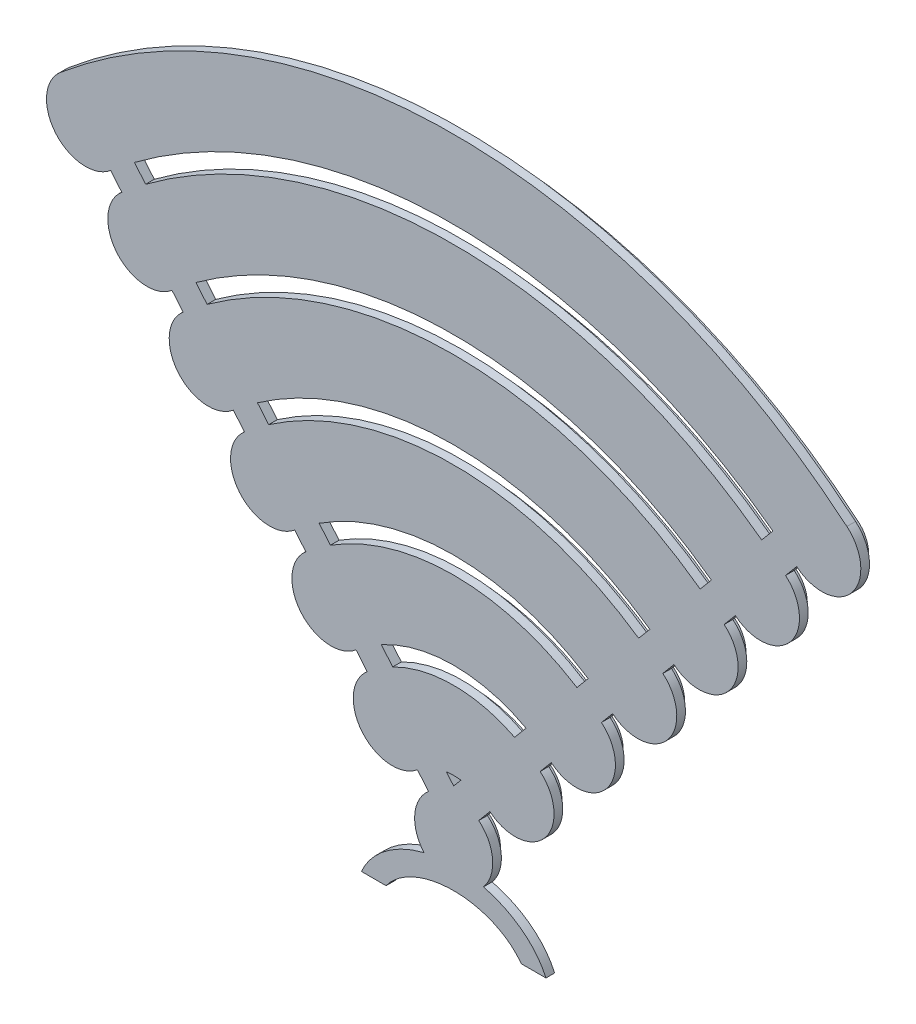
SolidWorks part; units mm, degrees
ref_plane "Front Plane" through (0, 0, 0) normal (0, 0, 1) x (1, 0, 0)
ref_plane "Top Plane" through (0, 0, 0) normal (0, 1, 0) x (1, 0, 0)
ref_plane "Right Plane" through (0, 0, 0) normal (1, 0, 0) x (0, 0, -1)
sketch "Sketch1" plane through (0, 0, 0) normal (0, 0, 1) x (1, 0, 0)
  line L0 (-84.848, 101.1179) -> (-70.7066, 84.2649) construction
  line L1 (-70.7066, 84.2649) -> (-56.5653, 67.4119) construction
  line L2 (-56.5653, 67.4119) -> (-42.424, 50.5589) construction
  line L3 (-42.424, 50.5589) -> (-28.2827, 33.706) construction
  line L4 (-28.2827, 33.706) -> (-14.1413, 16.853) construction
  line L5 (-14.1413, 16.853) -> (0, 0) construction
  line L6 (0, 172.6886) -> (0, -139.3712) construction
  line L7 (-79.0629, 94.2235) -> (-76.4917, 91.1593)
  line L8 (-64.9215, 77.3705) -> (-62.3504, 74.3063)
  line L9 (-50.7802, 60.5175) -> (-48.2091, 57.4533)
  line L10 (-36.6389, 43.6645) -> (-34.0677, 40.6004)
  line L11 (-22.4976, 26.8116) -> (-19.9264, 23.7474)
  line L12 (-8.3562, 9.9586) -> (-5.7851, 6.8944)
  line L13 (-73.5724, 98.5703) -> (-70.997, 95.501)
  line L14 (-59.4031, 81.684) -> (-56.8255, 78.6121)
  line L15 (-45.2182, 64.779) -> (-42.6363, 61.7021)
  line L16 (-30.9992, 47.8335) -> (-28.407, 44.7442)
  line L17 (-16.6807, 30.7694) -> (-14.0494, 27.6335)
  line L18 (-1.6791, 12.8911) -> (0, 10.8901)
  line L19 (14.1413, 16.853) -> (0, 0) construction
  line L20 (28.2827, 33.706) -> (14.1413, 16.853) construction
  line L21 (42.424, 50.5589) -> (28.2827, 33.706) construction
  line L22 (56.5653, 67.4119) -> (42.424, 50.5589) construction
  line L23 (70.7066, 84.2649) -> (56.5653, 67.4119) construction
  line L24 (84.848, 101.1179) -> (70.7066, 84.2649) construction
  line L25 (1.6791, 12.8911) -> (0, 10.8901)
  line L26 (16.6807, 30.7694) -> (14.0494, 27.6335)
  line L27 (30.9992, 47.8335) -> (28.407, 44.7442)
  line L28 (45.2182, 64.779) -> (42.6363, 61.7021)
  line L29 (59.4031, 81.684) -> (56.8255, 78.6121)
  line L30 (73.5724, 98.5703) -> (70.997, 95.501)
  line L31 (8.3562, 9.9586) -> (5.7851, 6.8944)
  line L32 (22.4976, 26.8116) -> (19.9264, 23.7474)
  line L33 (36.6389, 43.6645) -> (34.0677, 40.6004)
  line L34 (50.7802, 60.5175) -> (48.2091, 57.4533)
  line L35 (64.9215, 77.3705) -> (62.3504, 74.3063)
  line L36 (79.0629, 94.2235) -> (76.4917, 91.1593)
  line L37 (15.5746, -16.8) -> (21.273, -16.8)
  line L38 (0, -10) -> (0, -5) construction
  line L39 (-17.5, -22.5) -> (-22.5, -22.5) construction
  line L40 (-21.273, -16.8) -> (-15.5746, -16.8)
  line L41 (-15.5935, -17) -> (15.5935, -17) construction
  arc A0 (-5.7851, 6.8944) -> (-6.8548, -5.8319) centre (0, 0) ccw
  arc A1 (14.0494, 27.6335) -> (-14.0494, 27.6335) centre (0, 0) ccw
  arc A2 (1.6791, 12.8911) -> (-1.6791, 12.8911) centre (0, 0) ccw
  arc A3 (28.407, 44.7442) -> (-28.407, 44.7442) centre (0, 0) ccw
  arc A4 (16.6807, 30.7694) -> (-16.6807, 30.7694) centre (0, 0) ccw
  arc A5 (30.9992, 47.8335) -> (-30.9992, 47.8335) centre (0, 0) ccw
  arc A6 (42.6363, 61.7021) -> (-42.6363, 61.7021) centre (0, 0) ccw
  arc A7 (45.2182, 64.779) -> (-45.2182, 64.779) centre (0, 0) ccw
  arc A8 (56.8255, 78.6121) -> (-56.8255, 78.6121) centre (0, 0) ccw
  arc A9 (59.4031, 81.684) -> (-59.4031, 81.684) centre (0, 0) ccw
  arc A10 (70.997, 95.501) -> (-70.997, 95.501) centre (0, 0) ccw
  arc A11 (-19.9264, 23.7474) -> (-8.3562, 9.9586) centre (-14.1413, 16.853) ccw
  arc A12 (-34.0677, 40.6004) -> (-22.4976, 26.8116) centre (-28.2827, 33.706) ccw
  arc A13 (-48.2091, 57.4533) -> (-36.6389, 43.6645) centre (-42.424, 50.5589) ccw
  arc A14 (-62.3504, 74.3063) -> (-50.7802, 60.5175) centre (-56.5653, 67.4119) ccw
  arc A15 (-76.4917, 91.1593) -> (-64.9215, 77.3705) centre (-70.7066, 84.2649) ccw
  arc A16 (73.5724, 98.5703) -> (-73.5724, 98.5703) centre (0, 0) ccw
  arc A17 (90.6331, 108.0123) -> (-90.6331, 108.0123) centre (0, 0) ccw
  arc A18 (-90.6331, 108.0123) -> (-79.0629, 94.2235) centre (-84.848, 101.1179) ccw
  arc A19 (-5.7851, 6.8944) -> (5.7851, 6.8944) centre (0, 0) ccw construction
  arc A20 (90.6331, 108.0123) -> (79.0629, 94.2235) centre (84.848, 101.1179) cw
  arc A21 (76.4917, 91.1593) -> (64.9215, 77.3705) centre (70.7066, 84.2649) cw
  arc A22 (62.3504, 74.3063) -> (50.7802, 60.5175) centre (56.5653, 67.4119) cw
  arc A23 (48.2091, 57.4533) -> (36.6389, 43.6645) centre (42.424, 50.5589) cw
  arc A24 (34.0677, 40.6004) -> (22.4976, 26.8116) centre (28.2827, 33.706) cw
  arc A25 (19.9264, 23.7474) -> (8.3562, 9.9586) centre (14.1413, 16.853) cw
  arc A26 (6.8548, -5.8319) -> (5.7851, 6.8944) centre (0, 0) ccw
  ellipse E0 centre (0, -22.5) end of major axis (22.5, -22.5) minor radius 17.5 (21.273, -16.8) -> (6.8548, -5.8319) ccw
  ellipse E1 centre (0, -22.5) end of major axis (-17.5, -22.5) minor radius 12.5 (15.5746, -16.8) -> (-15.5746, -16.8) ccw
  ellipse E2 centre (0, -22.5) end of major axis (22.5, -22.5) minor radius 17.5 (-21.273, -16.8) -> (-6.8548, -5.8319) cw
  point P42 (0, -9)
  point P67 (0, 141)
  point P86 (-20, -22.5)
  point P91 (0, 0)
  point P94 (0, 0)
  dimension "D2" = 9
  dimension "D1" = 40
  dimension "D3" = 150
  dimension "D4" = 7
  dimension "D5" = 5
  dimension "D6" = 20
  dimension "D7" = 12.5
  dimension "D8" = 5
  dimension "D9" = 0.2
  dimension "D10" = 5
extrude "Boss-Extrude1" add sketch "Sketch1" along normal blind 1 and the other way blind 1
sketch "Sketch2" plane through (0, 0, -1) normal (0, 0, -1) x (-1, 0, 0)
  line L24 (30.7332, 40.049) -> (36.6028, 47.0441)
  line L25 (44.8746, 56.902) -> (50.7441, 63.8971)
  line L26 (59.0159, 73.755) -> (64.8855, 80.7501)
  line L27 (73.1572, 90.608) -> (79.0268, 97.6031)
  line L28 (-79.0268, 97.6031) -> (-73.1572, 90.608)
  line L29 (-64.8855, 80.7501) -> (-59.0159, 73.755)
  line L30 (-50.7441, 63.8971) -> (-44.8746, 56.902)
  line L31 (-36.6028, 47.0441) -> (-30.7332, 40.049)
  line L32 (-22.4615, 30.1911) -> (-16.5919, 23.1961)
  line L33 (-8.3202, 13.3382) -> (-2.4506, 6.3431)
  line L34 (2.4506, 6.3431) -> (8.3202, 13.3382)
  line L35 (16.5919, 23.1961) -> (22.4615, 30.1911)
  circle A1 centre (0, 0) radius 6.8
  arc A2 (74.8884, 100.3333) -> (-74.8884, 100.3333) centre (0, 0) ccw
  arc A3 (80.477, 95.9088) -> (-80.477, 95.9088) centre (0, 0) ccw
  arc A4 (6.8548, -5.8319) -> (5.7851, 6.8944) centre (0, 0) ccw construction
  arc A5 (81.7626, 97.4409) -> (-81.7626, 97.4409) centre (0, 0) ccw
  arc A6 (-87.9333, 104.7949) -> (-81.7626, 97.4409) centre (-84.848, 101.1179) ccw
  arc A7 (87.9333, 104.7949) -> (-87.9333, 104.7949) centre (0, 0) ccw
  arc A8 (81.7626, 97.4409) -> (87.9333, 104.7949) centre (84.848, 101.1179) ccw
  arc A9 (73.792, 87.9419) -> (-73.792, 87.9419) centre (0, 0) ccw
  arc A10 (-73.792, 87.9419) -> (-67.6213, 80.5879) centre (-70.7066, 84.2649) ccw
  arc A11 (67.6213, 80.5879) -> (-67.6213, 80.5879) centre (0, 0) ccw
  arc A12 (69.6844, 93.7354) -> (-69.6844, 93.7354) centre (0, 0) ccw
  arc A13 (75.0776, 89.474) -> (-75.0776, 89.474) centre (0, 0) ccw
  arc A14 (67.6213, 80.5879) -> (73.792, 87.9419) centre (70.7066, 84.2649) ccw
  arc A15 (25.1973, 30.0289) -> (31.368, 37.383) centre (28.2827, 33.706) ccw
  arc A16 (31.368, 37.383) -> (-31.368, 37.383) centre (0, 0) ccw
  arc A17 (-31.368, 37.383) -> (-25.1973, 30.0289) centre (-28.2827, 33.706) ccw
  arc A18 (25.1973, 30.0289) -> (-25.1973, 30.0289) centre (0, 0) ccw
  arc A19 (39.3386, 46.8819) -> (45.5094, 54.2359) centre (42.424, 50.5589) ccw
  arc A20 (45.5094, 54.2359) -> (-45.5094, 54.2359) centre (0, 0) ccw
  arc A21 (-45.5094, 54.2359) -> (-39.3386, 46.8819) centre (-42.424, 50.5589) ccw
  arc A22 (39.3386, 46.8819) -> (-39.3386, 46.8819) centre (0, 0) ccw
  arc A23 (53.4799, 63.7349) -> (59.6507, 71.0889) centre (56.5653, 67.4119) ccw
  arc A24 (59.6507, 71.0889) -> (-59.6507, 71.0889) centre (0, 0) ccw
  arc A25 (-59.6507, 71.0889) -> (-53.4799, 63.7349) centre (-56.5653, 67.4119) ccw
  arc A26 (53.4799, 63.7349) -> (-53.4799, 63.7349) centre (0, 0) ccw
  arc A27 (-17.2267, 20.53) -> (-11.0559, 13.176) centre (-14.1413, 16.853) ccw
  arc A28 (22.4615, 30.1911) -> (30.7332, 40.049) centre (28.2827, 33.706) ccw
  arc A29 (36.6028, 47.0441) -> (44.8746, 56.902) centre (42.424, 50.5589) ccw
  arc A30 (50.7441, 63.8971) -> (59.0159, 73.755) centre (56.5653, 67.4119) ccw
  arc A31 (64.8855, 80.7501) -> (73.1572, 90.608) centre (70.7066, 84.2649) ccw
  arc A32 (79.0268, 97.6031) -> (89.2189, 106.327) centre (84.848, 101.1179) ccw
  arc A33 (89.2189, 106.327) -> (-89.2189, 106.327) centre (0, 0) ccw
  arc A34 (-89.2189, 106.327) -> (-79.0268, 97.6031) centre (-84.848, 101.1179) ccw
  arc A35 (-73.1572, 90.608) -> (-64.8855, 80.7501) centre (-70.7066, 84.2649) ccw
  arc A36 (-59.0159, 73.755) -> (-50.7441, 63.8971) centre (-56.5653, 67.4119) ccw
  arc A37 (-44.8746, 56.902) -> (-36.6028, 47.0441) centre (-42.424, 50.5589) ccw
  arc A38 (-30.7332, 40.049) -> (-22.4615, 30.1911) centre (-28.2827, 33.706) ccw
  arc A39 (-16.5919, 23.1961) -> (-8.3202, 13.3382) centre (-14.1413, 16.853) ccw
  arc A40 (-2.4506, 6.3431) -> (2.4506, 6.3431) centre (0, 0) ccw
  arc A41 (8.3202, 13.3382) -> (16.5919, 23.1961) centre (14.1413, 16.853) ccw
  arc A42 (23.9117, 28.4969) -> (32.6536, 38.9151) centre (28.2827, 33.706) ccw
  arc A43 (38.053, 45.3498) -> (46.7949, 55.768) centre (42.424, 50.5589) ccw
  arc A44 (52.1944, 62.2028) -> (60.9363, 72.621) centre (56.5653, 67.4119) ccw
  arc A45 (66.3357, 79.0558) -> (75.0776, 89.474) centre (70.7066, 84.2649) ccw
  arc A46 (80.477, 95.9088) -> (89.2189, 106.327) centre (84.848, 101.1179) ccw
  arc A47 (89.2189, 106.327) -> (-89.2189, 106.327) centre (0, 0) ccw
  arc A48 (-89.2189, 106.327) -> (-80.477, 95.9088) centre (-84.848, 101.1179) ccw
  arc A49 (-75.0776, 89.474) -> (-66.3357, 79.0558) centre (-70.7066, 84.2649) ccw
  arc A50 (-60.9363, 72.621) -> (-52.1944, 62.2028) centre (-56.5653, 67.4119) ccw
  arc A51 (-46.7949, 55.768) -> (-38.053, 45.3498) centre (-42.424, 50.5589) ccw
  arc A52 (-32.6536, 38.9151) -> (-23.9117, 28.4969) centre (-28.2827, 33.706) ccw
  arc A53 (-18.5123, 22.0621) -> (-9.7704, 11.6439) centre (-14.1413, 16.853) ccw
  arc A54 (11.0559, 13.176) -> (-11.0559, 13.176) centre (0, 0) ccw
  arc A55 (9.7704, 11.6439) -> (18.5123, 22.0621) centre (14.1413, 16.853) ccw
  arc A56 (11.0559, 13.176) -> (17.2267, 20.53) centre (14.1413, 16.853) ccw
  arc A57 (60.6971, 83.4632) -> (-60.6971, 83.4632) centre (0, 0) ccw
  arc A58 (66.3357, 79.0558) -> (-66.3357, 79.0558) centre (0, 0) ccw
  arc A59 (17.2267, 20.53) -> (-17.2267, 20.53) centre (0, 0) ccw
  arc A60 (55.5367, 76.8291) -> (-55.5367, 76.8291) centre (0, 0) ccw
  arc A61 (60.9363, 72.621) -> (-60.9363, 72.621) centre (0, 0) ccw
  circle A62 centre (0, 0) radius 4.8
  arc A63 (46.4774, 66.583) -> (-46.4774, 66.583) centre (0, 0) ccw
  arc A64 (52.1944, 62.2028) -> (-52.1944, 62.2028) centre (0, 0) ccw
  arc A66 (41.3857, 59.8921) -> (-41.3857, 59.8921) centre (0, 0) ccw
  arc A67 (46.7949, 55.768) -> (-46.7949, 55.768) centre (0, 0) ccw
  arc A69 (32.1957, 49.6797) -> (-32.1957, 49.6797) centre (0, 0) ccw
  arc A70 (38.053, 45.3498) -> (-38.053, 45.3498) centre (0, 0) ccw
  arc A72 (27.2278, 42.8869) -> (-27.2278, 42.8869) centre (0, 0) ccw
  arc A73 (32.6536, 38.9151) -> (-32.6536, 38.9151) centre (0, 0) ccw
  arc A75 (17.7292, 32.7034) -> (-17.7292, 32.7034) centre (0, 0) ccw
  arc A76 (23.9117, 28.4969) -> (-23.9117, 28.4969) centre (0, 0) ccw
  arc A78 (13.0524, 25.6725) -> (-13.0524, 25.6725) centre (0, 0) ccw
  arc A79 (18.5123, 22.0621) -> (-18.5123, 22.0621) centre (0, 0) ccw
  arc A81 (1.9632, 15.0727) -> (-1.9632, 15.0727) centre (0, 0) ccw
  arc A82 (9.7704, 11.6439) -> (-9.7704, 11.6439) centre (0, 0) ccw
  dimension "D13" = 2.2
  dimension "D1" = 2.2
  dimension "D2" = 2.2
  dimension "D3" = 2.2
  dimension "D4" = 2.2
  dimension "D5" = 2.2
  dimension "D6" = 2.2
  dimension "D7" = 2.2
  dimension "D8" = 2.2
  dimension "D9" = 2.2
  dimension "D10" = 2.2
  dimension "D11" = 2.2
  dimension "D12" = 2.2
  dimension "D14" = 2
  dimension "D15" = 2
extrude "Boss-Extrude2" add sketch "Sketch2" along normal blind 2
